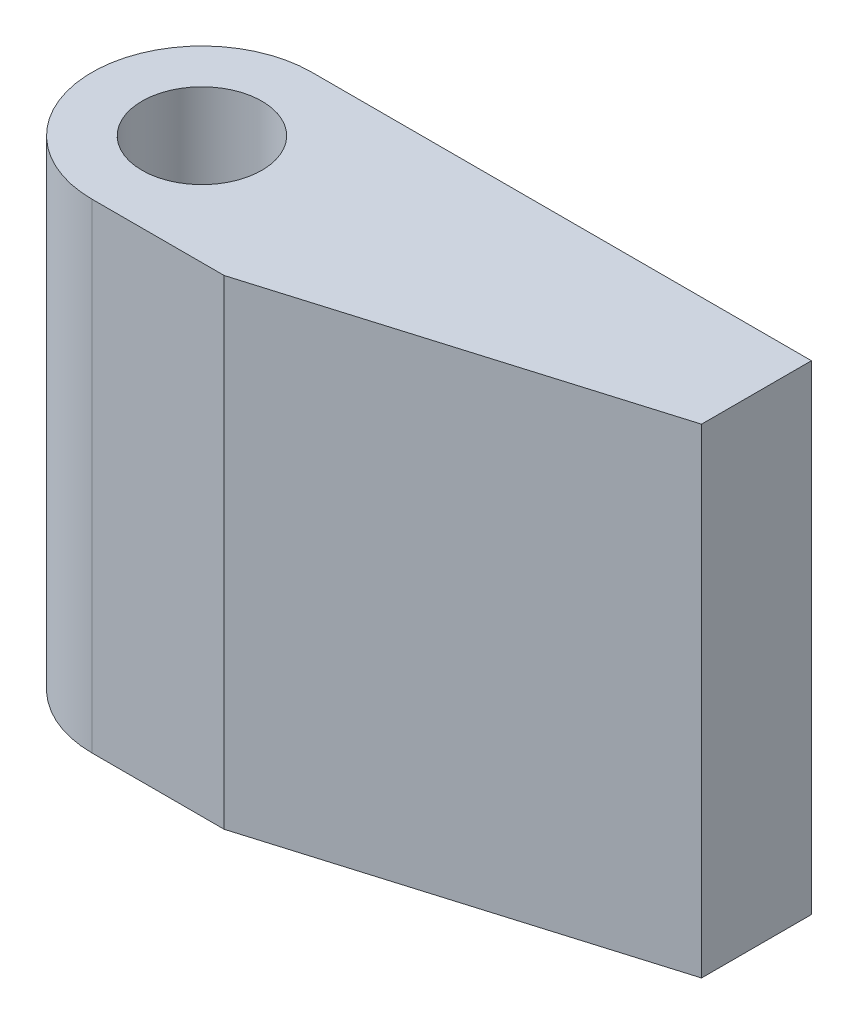
SolidWorks part; units mm, degrees
ref_plane "Front Plane" through (0, 0, 0) normal (0, 0, 1) x (1, 0, 0)
ref_plane "Top Plane" through (0, 0, 0) normal (0, 1, 0) x (1, 0, 0)
ref_plane "Right Plane" through (0, 0, 0) normal (1, 0, 0) x (0, 0, -1)
sketch "Sketch2" plane through (0, 0, 0) normal (0, 1, 0) x (1, 0, 0)
  line L0 (0, 2.2) -> (10, 2.2)
  line L1 (10, 2.2) -> (10, -2.2)
  line L2 (10, -2.2) -> (0, -2.2)
  arc A1 (0, 2.2) -> (0, -2.2) centre (0, 0) ccw
extrude "Boss-Extrude1" add sketch "Sketch2" along normal blind 5 and the other way blind 5 contours L2 A1 L0 L1
sketch "Sketch3" plane through (0, 5, 0) normal (0, 1, 0) x (1, 0, 0)
  circle A0 centre (0, 0) radius 1.2
extrude "Cut-Extrude1" cut sketch "Sketch3" against normal blind 10 contours A0
sketch "Sketch4" plane through (0, -5, 0) normal (0, -1, 0) x (1, 0, 0)
  line L1 (10, 2.2) -> (-3.3746, 2.2)
  line L2 (10, 2.2) -> (10, -2.5981)
  line L3 (10, -2.5981) -> (-3.3746, -2.5981)
  line L4 (-3.3746, 2.2) -> (-3.3746, -2.5981)
extrude "Cut-Extrude2" cut sketch "Sketch4" against normal blind 0.2 contours L4 L3 L2 L1
mirror "Mirror1" about plane through (0, 0, 0) normal (0, 1, 0) of "Cut-Extrude2"
sketch "Sketch5" plane through (0, 4.8, 0) normal (0, 1, 0) x (1, 0, 0)
  line L0 (2.6453, -2.2) -> (10, 0)
  line L1 (10, -2.2) -> (0, -2.2) construction
  line L2 (10, -2.2) -> (10, 2.2) construction
  line L3 (10, 0) -> (10, -2.2)
  line L4 (10, -2.2) -> (2.6453, -2.2)
extrude "Cut-Extrude3" cut sketch "Sketch5" against normal blind 10
